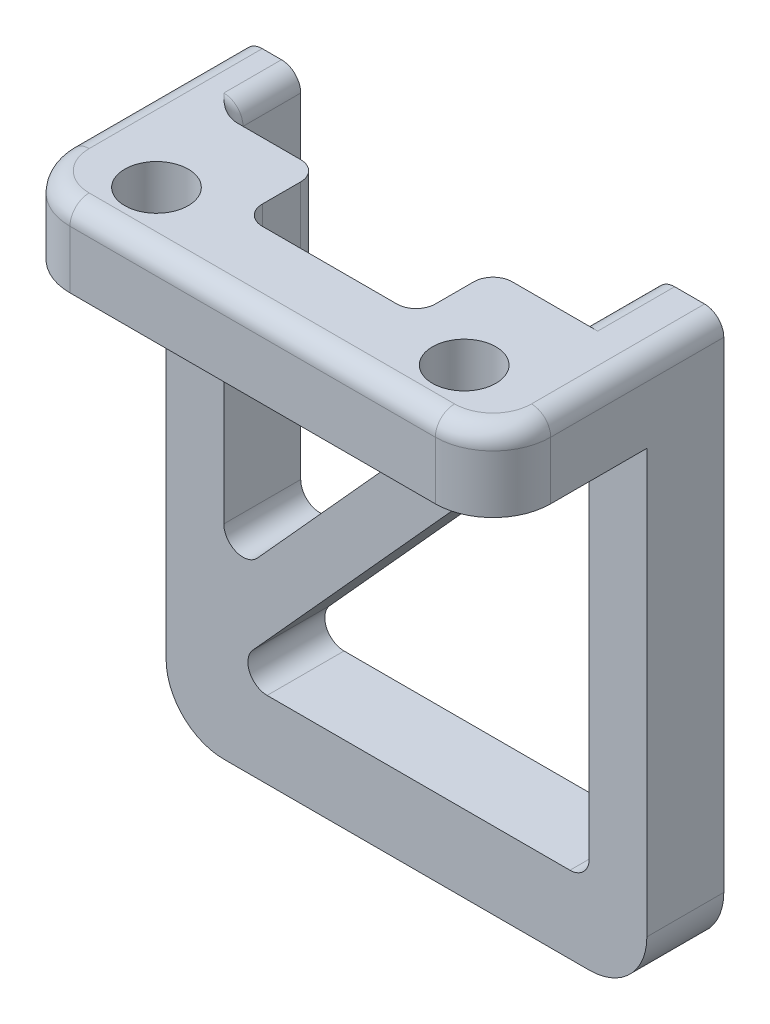
SolidWorks part; units mm, degrees
material "ABS"
ref_plane "前视基准面" through (0, 0, 0) normal (0, 0, 1) x (1, 0, 0)
ref_plane "上视基准面" through (0, 0, 0) normal (0, 1, 0) x (1, 0, 0)
ref_plane "右视基准面" through (0, 0, 0) normal (1, 0, 0) x (0, 0, -1)
sketch "草图1" plane through (0, 0, 0) normal (0, 0, 1) x (1, 0, 0)
  line L1 (-12.5, 12.5) -> (12.5, 12.5)
  line L2 (-12.5, 12.5) -> (-12.5, -12.5)
  line L3 (-12.5, -12.5) -> (12.5, -12.5)
  line L4 (12.5, 12.5) -> (12.5, -12.5)
  line L5 (-12.5, 12.5) -> (12.5, -12.5) construction
  line L6 (-12.5, -12.5) -> (12.5, 12.5) construction
  point P0 (0, 0)
  dimension "D1" = 25
extrude "凸台-拉伸1" add sketch "草图1" along normal blind 4
sketch "草图2" plane through (0, 0, 0) normal (0, 0, -1) x (-1, 0, 0)
  line L0 (0, 0) -> (0, 14.5) construction
  line L2 (-12.5, 16.5) -> (12.5, 16.5)
  line L3 (-12.5, 16.5) -> (-12.5, 12.5)
  line L4 (-12.5, 12.5) -> (12.5, 12.5)
  line L5 (12.5, 16.5) -> (12.5, 12.5)
  line L6 (-12.5, 16.5) -> (12.5, 12.5) construction
  line L7 (-12.5, 12.5) -> (12.5, 16.5) construction
  dimension "D1" = 4
extrude "凸台-拉伸2" add sketch "草图2" against normal blind 12
sketch "草图3" plane through (0, 16.5, 0) normal (0, 1, 0) x (1, 0, 0)
  line L0 (0, 0) -> (0, -12) construction
  line L1 (-12.5, 0) -> (12.5, 0) construction
  line L2 (-12.5, -12) -> (12.5, -12) construction
  circle A0 centre (-8, -9) radius 1.65
  circle A1 centre (8, -9) radius 1.65
  dimension "D1" = 3.3
  dimension "D3" = 8
  dimension "D2" = 9
extrude "切除-拉伸1" cut sketch "草图3" against normal through all
fillet "圆角1" radius 3 4 edges at (-12.5, 14.5, 12) (12.5, 14.5, 12) (-12.5, -12.5, 2) (12.5, -12.5, 2)
sketch "草图4" plane through (0, 16.5, 0) normal (0, 1, 0) x (1, 0, 0)
  line L0 (-12.5, 0) -> (12.5, 0) construction
  line L1 (-9.5, 0) -> (9.5, 0)
  line L2 (0, 0) -> (0, -12) construction
  line L3 (-9.5, -12) -> (9.5, -12) construction
  line L4 (9.5, 0) -> (9.5, -4)
  line L5 (9.5, -4) -> (4.5, -4)
  line L6 (4.5, -4) -> (4.5, -8)
  line L7 (4.5, -8) -> (-4.5, -8)
  line L8 (12.5, -9) -> (12.5, 0) construction
  line L9 (-4.5, -4) -> (-4.5, -8)
  line L10 (-9.5, 0) -> (-9.5, -4)
  line L11 (-9.5, -4) -> (-4.5, -4)
  circle A0 centre (8, -9) radius 1.65 construction
  point P16 (0, -8)
  dimension "D1" = 3
  dimension "D2" = 4
  dimension "D3" = 3.5
  dimension "D4" = 5
extrude "切除-拉伸2" cut sketch "草图4" against normal blind 25
sketch "草图5" plane through (0, 0, 0) normal (0, 0, -1) x (-1, 0, 0)
  line L0 (-9.5, 12.5) -> (9.5, -8.5)
  line L1 (-9.5, 12.5) -> (-9.5, 16.5)
  line L3 (-9.5, 16.5) -> (9.5, -4.5)
  line L4 (9.5, -8.5) -> (9.5, 16.5) construction
  line L5 (9.5, -4.5) -> (9.5, -8.5)
extrude "凸台-拉伸3" add sketch "草图5" against normal up to surface (4 mm away) up to face at (7, 14.5, 4)
fillet "圆角2" radius 1 11 edges at (-11.6213, 16.5, 11.1213) (0, 16.5, 12) (11.6213, 16.5, 11.1213) (-9.5, -4.5, 2) (-9.5, 16.5, 2) (-12.5, 16.5, 4.5) (12.5, 16.5, 4.5) (9.5, 16.5, 2) (9.5, -8.5, 2) (-9.5, -8.5, 2) (9.5, 12.5, 2)
fillet "圆角3" radius 1 6 edges at (-9.7929, 16.2071, 4) (-9.5, 14, 4) (-4.5, 14.5, 4) (-4.5, 14.5, 8) (4.5, 14.5, 8) (4.5, 14.5, 4)
